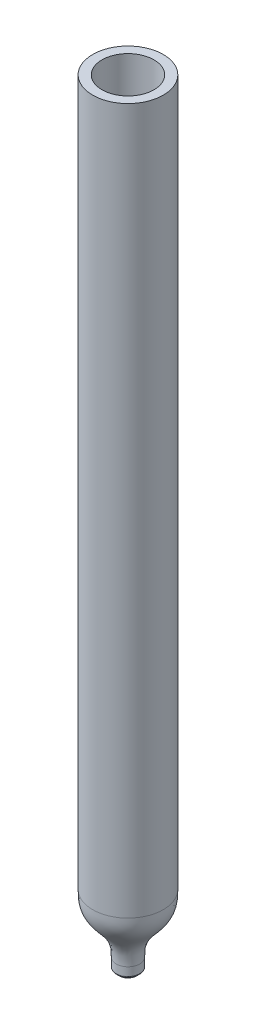
SolidWorks part; units mm, degrees
material "Glass"
ref_plane "Front Plane" through (0, 0, 0) normal (0, 0, 1) x (1, 0, 0)
ref_plane "Top Plane" through (0, 0, 0) normal (0, 1, 0) x (1, 0, 0)
ref_plane "Right Plane" through (0, 0, 0) normal (1, 0, 0) x (0, 0, -1)
sketch "Sketch1" plane through (0, 0, 0) normal (0, 0, 1) x (1, 0, 0)
  line L0 (2.21, 0) -> (0, 0) construction
  line L1 (2.21, 61) -> (3, 61)
  line L2 (2.21, 61) -> (2.21, 0)
  line L3 (0.25, -4) -> (1, -4) construction
  line L4 (3, 61) -> (3, 1)
  line L5 (0, 0) -> (0, -17.1222) construction
  line L6 (3, 1) -> (2.21, 1) construction
  line L8 (0.25, -4) -> (0.25, -5)
  line L9 (0.25, -5) -> (1, -5)
  line L10 (1, -4) -> (1, -5)
  spline S0 degree 5 poles (0.25, -4) (0.25, -2.8701) (0.25, -1.7403) (2.21, -2.2597) (2.21, -1.1299) (2.21, 0) knots 0 0 0 0 0 0 1 1 1 1 1 1
  spline S1 degree 5 poles (1, -4) (1, -2.8523) (1, -1.7047) (3, -1.2953) (3, -0.1477) (3, 1) knots 0 0 0 0 0 0 1 1 1 1 1 1
  dimension "D1" = 6
  dimension "D2" = 4.42
  dimension "D3" = 60
  dimension "D4" = 5
  dimension "D5" = 4
  dimension "D6" = 0.5
  dimension "D7" = 2
  dimension "D8" = 1
revolve "Revolve1" add sketch "Sketch1" angle 360 about L5
chamfer "Chamfer1" distance 0.25 angle 45 1 edges at (0, -5, 1)
fillet "Fillet1" radius 0.1 1 edges at (0, -4.75, 1)
